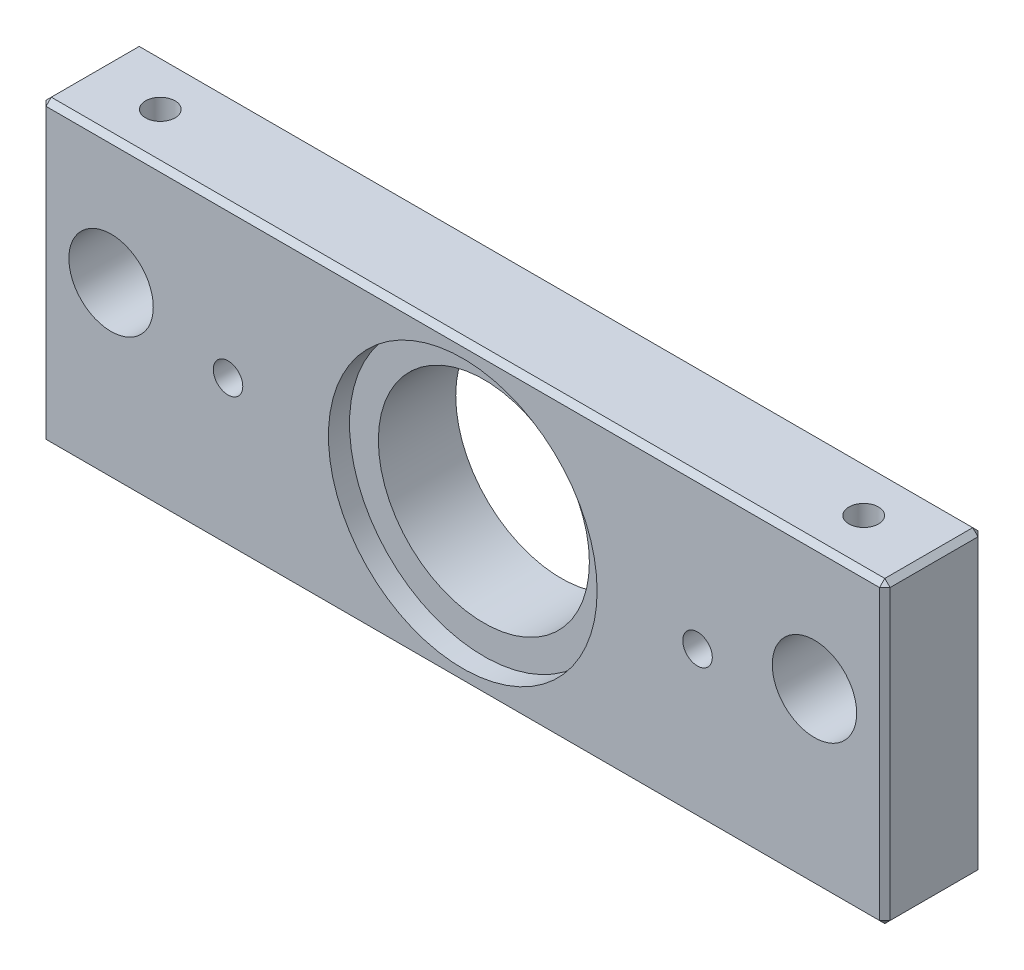
SolidWorks part; units mm, degrees
ref_plane "Front Plane" through (0, 0, 0) normal (0, 0, 1) x (1, 0, 0)
ref_plane "Top Plane" through (0, 0, 0) normal (0, 1, 0) x (1, 0, 0)
ref_plane "Right Plane" through (0, 0, 0) normal (1, 0, 0) x (0, 0, -1)
sketch "Sketch1" plane through (0, 0, 0) normal (0, 0, 1) x (1, 0, 0)
  line L1 (-60, -21.25) -> (60, -21.25)
  line L2 (-60, -21.25) -> (-60, 21.25)
  line L3 (-60, 21.25) -> (60, 21.25)
  line L4 (60, -21.25) -> (60, 21.25)
  line L5 (-60, -21.25) -> (60, 21.25) construction
  line L6 (-60, 21.25) -> (60, -21.25) construction
  point P0 (0, 0)
  dimension "D1" = 120
  dimension "D2" = 42.5
extrude "Boss-Extrude1" add sketch "Sketch1" along normal mid plane 14
sketch "Sketch2" plane through (0, 0, 7) normal (0, 0, 1) x (1, 0, 0)
  circle A0 centre (0, 0) radius 19.1
  dimension "D1" = 38.2
extrude "Cut-Extrude1" cut sketch "Sketch2" against normal blind 3
sketch "Sketch3" plane through (0, 0, 4) normal (0, 0, 1) x (1, 0, 0)
  circle A0 centre (0, 0) radius 15
extrude "Cut-Extrude2" cut sketch "Sketch3" against normal through all
sketch "Sketch4" plane through (0, 0, 7) normal (0, 0, 1) x (1, 0, 0)
  circle A0 centre (-33.375, 0) radius 2.1
  circle A1 centre (33.375, 0) radius 2.1
  dimension "D1" = 4.2
  dimension "D2" = 4.2
  dimension "D3" = 33.375
  dimension "D4" = 33.375
extrude "Cut-Extrude3" cut sketch "Sketch4" against normal through all
sketch "Sketch5" plane through (0, 0, 7) normal (0, 0, 1) x (1, 0, 0)
  line L0 (-40.6477, 3.4) -> (36.4799, 3.4) construction
  circle A0 centre (-50, 3.4) radius 6
  circle A1 centre (50, 3.4) radius 6
  dimension "D1" = 12
  dimension "D2" = 12
  dimension "D4" = 50
  dimension "D3" = 50
  dimension "D5" = 3.4
extrude "Cut-Extrude4" cut sketch "Sketch5" against normal through all
sketch "Sketch6" plane through (0, -21.25, 0) normal (0, -1, 0) x (1, 0, 0)
  line L0 (-60, 0) -> (60, 0) construction
  line L1 (-60, 7) -> (-60, -7) construction
  line L2 (60, 7) -> (60, -7) construction
  circle A0 centre (-50, 0) radius 2.1
  circle A1 centre (-25, 0) radius 2.1
  circle A2 centre (25, 0) radius 2.1
  circle A3 centre (50, 0) radius 2.1
  circle A4 centre (-37.5, 0) radius 1.25
  circle A5 centre (37.5, 0) radius 1.25
  dimension "D1" = 4.2
  dimension "D2" = 4.2
  dimension "D3" = 4.2
  dimension "D4" = 4.2
  dimension "D5" = 10
  dimension "D9" = 2.5
  dimension "D10" = 2.5
  dimension "D11" = 22.5
  dimension "D12" = 22.5
  dimension "D6" = 35
  dimension "D7" = 10
  dimension "D8" = 35
extrude "Cut-Extrude5" cut sketch "Sketch6" against normal blind 10
chamfer "Chamfer1" distance 0.75 angle 45 12 edges at (60, -21.25, 0) (60, 0, -7) (60, 21.25, 0) (0, -21.25, -7) (-60, -21.25, 0) (-60, 0, -7) (0, 21.25, -7) (-60, 21.25, 0) (60, 0, 7) (0, -21.25, 7) (-60, 0, 7) (0, 21.25, 7)
sketch "Sketch7" plane through (0, 21.25, 0) normal (0, 1, 0) x (1, 0, 0)
  line L0 (-1000, 0) -> (49000, 0) construction
  circle A0 centre (-50, 0) radius 2.1
  circle A1 centre (50, 0) radius 2.1
  dimension "D1" = 50
  dimension "D2" = 50
  dimension "D3" = 4.2
  dimension "D4" = 4.2
extrude "Cut-Extrude6" cut sketch "Sketch7" against normal up to next
equation "\"D4@Sketch4\"=\"D3@Sketch4\""
